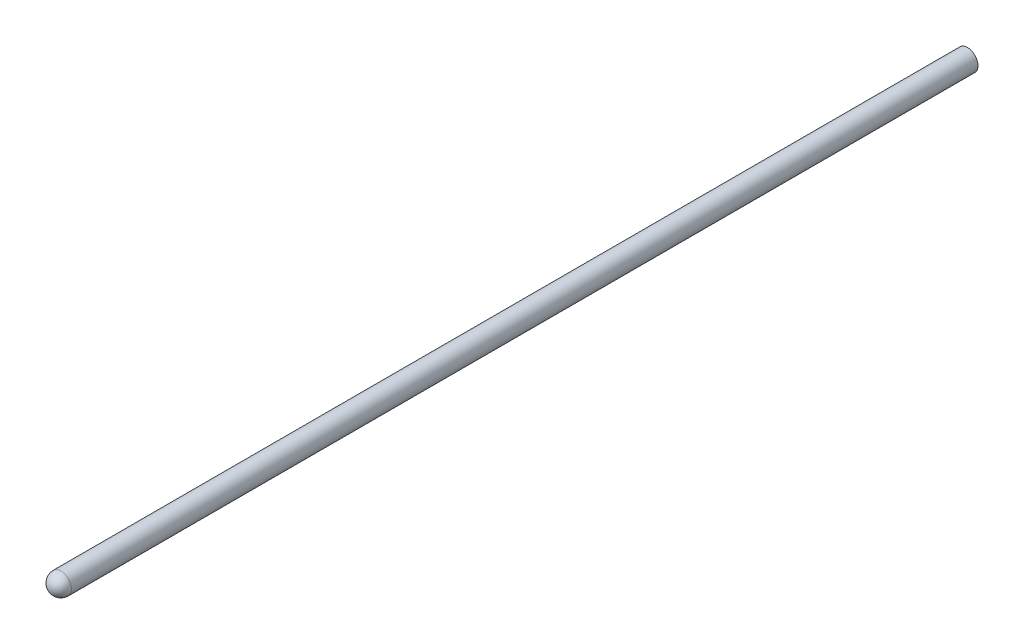
SolidWorks part; units mm, degrees
ref_plane "Front Plane" through (0, 0, 0) normal (0, 0, 1) x (1, 0, 0)
ref_plane "Top Plane" through (0, 0, 0) normal (0, 1, 0) x (1, 0, 0)
ref_plane "Right Plane" through (0, 0, 0) normal (1, 0, 0) x (0, 0, -1)
sketch "Sketch1" plane through (0, 0, 0) normal (0, 0, 1) x (1, 0, 0)
  circle A0 centre (0, 0) radius 6.35
  dimension "D1" = 12.7
extrude "Boss-Extrude1" add sketch "Sketch1" against normal mid plane 546.1
sketch "Sketch3" plane through (0, 0, 0) normal (0, 1, 0) x (1, 0, 0)
  line L0 (6.35, 273.05) -> (6.35, -273.05) construction
dome "Dome2" faces to dome 1 distance 6.35 reverse direction no elliptical dome no face at (6.35, 0, 273.05) parameters "D1"=6.35
sketch "Sketch4" plane through (0, 0, 0) normal (0, 1, 0) x (1, 0, 0)
  arc A0 (-6.35, -273.05) -> (6.35, -273.05) centre (0, -273.05) ccw construction
  point P0 (0, -279.4)
